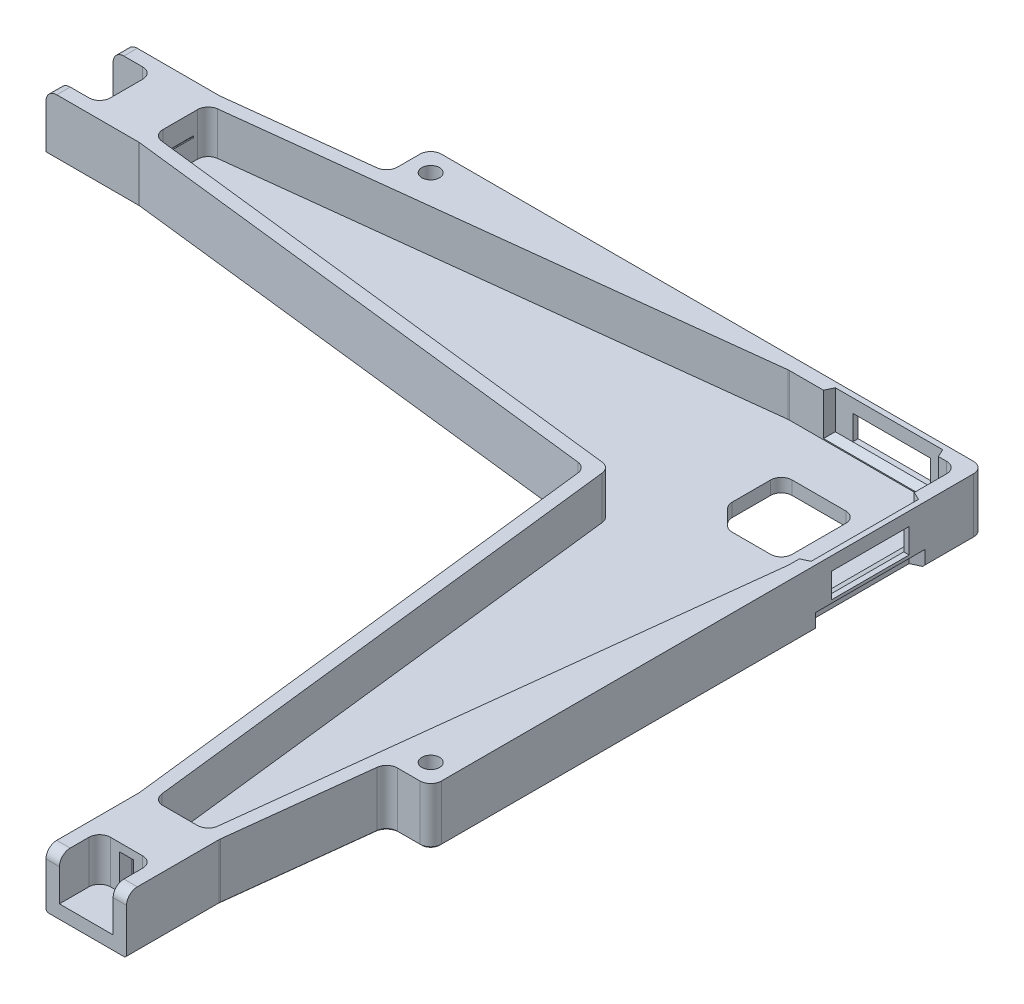
SolidWorks part; units mm, degrees
ref_plane "Front Plane" through (0, 0, 0) normal (0, 0, 1) x (1, 0, 0)
ref_plane "Top Plane" through (0, 0, 0) normal (0, 1, 0) x (1, 0, 0)
ref_plane "Right Plane" through (0, 0, 0) normal (1, 0, 0) x (0, 0, -1)
sketch "x Sensor" plane through (0, 0, 0) normal (0, 0, 1) x (1, 0, 0)
  line L0 (-13, 0) -> (0, 0) construction
  line L1 (-22.5, 1.5) -> (-13, 1.5)
  line L2 (-22.5, 1.5) -> (-22.5, -1.5)
  line L3 (-22.5, -1.5) -> (-13, -1.5)
  line L4 (-13, 1.5) -> (-13, -1.5)
  point P4 (-13, 0)
  dimension "D1" = 13
  dimension "D2" = 3
  dimension "D3" = 9.5
sketch "y Sensor" plane through (0, 0, 0) normal (1, 0, 0) x (0, 0, -1)
  line L0 (-13, 0) -> (0, 0) construction
  line L1 (-13, 1.5) -> (-22.5, 1.5)
  line L2 (-13, 1.5) -> (-13, -1.5)
  line L3 (-13, -1.5) -> (-22.5, -1.5)
  line L4 (-22.5, 1.5) -> (-22.5, -1.5)
  line L5 (0, 1.5) -> (0, -1.5) construction
  dimension "D1" = 9.5
  dimension "D2" = 13
ref_plane "y LED plane" through (-130, 0, 0) normal (1, 0, 0) x (0, 0, -1)
ref_plane "x LED plane" through (0, 0, 130) normal (0, 0, 1) x (1, 0, 0)
sketch "y LED" plane through (-130, 0, 0) normal (1, 0, 0) x (0, 0, -1)
  line L0 (-17.75, 1.5) -> (-17.75, -1.5) construction
  line L1 (-13, 1.5) -> (-22.5, 1.5) construction
  line L2 (-13, -1.5) -> (-22.5, -1.5) construction
  line L3 (-22.75, 0) -> (-12.75, 0) construction
  line L4 (-13, 0) -> (0, 0) construction
  point P10 (-17.75, 0)
  point P11 (-17.75, 0)
  dimension "D1" = 10
sketch "x LED" plane through (0, 0, 130) normal (0, 0, 1) x (1, 0, 0)
  line L0 (-17.75, 1.5) -> (-17.75, -1.5) construction
  line L1 (-22.5, 1.5) -> (-13, 1.5) construction
  line L2 (-22.5, -1.5) -> (-13, -1.5) construction
  line L3 (-22.75, 0) -> (-12.75, 0) construction
  point P9 (-17.75, 0)
  point P10 (-17.75, 0)
  dimension "D1" = 10
ref_plane "y LED cross-plane" through (0, 0, 17.75) normal (0, 0, 1) x (0, -1, 0)
ref_plane "x LED cross-plane" through (-17.75, 0, 0) normal (1, 0, 0) x (0, -1, 0)
ref_plane "Floor plane" through (0, -4, 0) normal (0, 1, 0) x (1, 0, 0)
ref_plane "Ceiling plane" through (0, 4, 0) normal (0, 1, 0) x (1, 0, 0)
sketch "Sketch10" plane through (0, -4, 0) normal (0, 1, 0) x (1, 0, 0)
  line L0 (0, 0) -> (-20, 0)
  line L1 (-20, 0) -> (-130, -12.75)
  line L2 (-130, -22.75) -> (-130, -12.75) construction
  line L3 (-130, -12.75) -> (-145, -12.75)
  line L4 (-145, -12.75) -> (-145, -22.75) construction
  line L5 (-145, -22.75) -> (-130, -22.75)
  line L6 (-130, -22.75) -> (-33.89, -33.89)
  line L7 (-20, -35.5) -> (-130, -22.75) construction
  line L8 (-33.89, -33.89) -> (-22.75, -130)
  line L9 (-22.75, -130) -> (-12.75, -130) construction
  line L10 (-22.75, -130) -> (-22.75, -145)
  line L11 (-22.75, -145) -> (-12.75, -145) construction
  line L12 (-12.75, -145) -> (-12.75, -130)
  line L13 (-12.75, -130) -> (0, -20)
  line L14 (0, -20) -> (0, 0)
  line L15 (-145, -17.75) -> (-51.5337, -17.75) construction
  line L16 (-17.75, -145) -> (-17.75, -69.9842) construction
  line L17 (-20.1444, 2.5) -> (-130.1444, -10.25)
  line L18 (-130.1444, -10.25) -> (-147.5, -10.25)
  line L19 (-147.5, -10.25) -> (-147.5, -12.75)
  line L20 (-147.5, -25.25) -> (-130.1444, -25.25)
  line L21 (-130.1444, -25.25) -> (-36.1453, -36.1453)
  line L23 (-36.1453, -36.1453) -> (-25.25, -130.1444)
  line L24 (-25.25, -130.1444) -> (-25.25, -147.5)
  line L25 (-25.25, -147.5) -> (-22.75, -147.5)
  line L26 (-10.25, -147.5) -> (-10.25, -130.1444)
  line L27 (-10.25, -130.1444) -> (2.5, -20.1444)
  line L28 (2.5, -20.1444) -> (2.5, 2.5)
  line L29 (2.5, 2.5) -> (-20.1444, 2.5)
  line L30 (-145, -12.75) -> (-147.5, -12.75)
  line L31 (-145, -22.75) -> (-147.5, -22.75)
  line L32 (-147.5, -12.75) -> (-147.5, -22.75) construction
  line L33 (-147.5, -10.25) -> (-147.5, -25.25) construction
  line L34 (-147.5, -22.75) -> (-147.5, -25.25)
  line L35 (-22.75, -145) -> (-22.75, -147.5)
  line L36 (-12.75, -145) -> (-12.75, -147.5)
  line L37 (-22.75, -147.5) -> (-12.75, -147.5) construction
  line L38 (-25.25, -147.5) -> (-10.25, -147.5) construction
  line L39 (-12.75, -147.5) -> (-10.25, -147.5)
  line L40 (-15.8451, -35.9816) -> (-33.89, -33.89) construction
  line L41 (-36.1453, -36.1453) -> (-36.1453, -36.1453) construction
  line L42 (-22.75, -130) -> (-35.5, -20) construction
  line L43 (-130.1444, -25.25) -> (-36.1453, -36.1453) construction
  line L44 (-130, -22.75) -> (-15.8451, -35.9816) construction
  dimension "D2" = 20
  dimension "D3" = 15
  dimension "D4" = 2.5
sketch "Max Shadows" plane through (0, 0, 0) normal (0, 1, 0) x (1, 0, 0)
  line L0 (-130, -17.75) -> (0, -13) construction
  line L1 (0, -13) -> (0, -22.5) construction
  line L2 (0, -22.5) -> (-130, -17.75) construction
  line L3 (0, -20) -> (0, 0) construction
  line L4 (-17.75, -130) -> (-22.5, 0) construction
  line L5 (-22.75, -130) -> (-12.75, -130) construction
  line L6 (-22.5, 0) -> (-13, 0) construction
  line L7 (0, 0) -> (-20, 0) construction
  line L8 (-17.75, -130) -> (-13, 0) construction
extrude "Boss-Extrude3" add sketch "Sketch10" along normal up to surface (8 mm away) up to plane "Ceiling plane"
sketch "Sketch12" plane through (0, -4, 0) normal (0, 1, 0) x (1, 0, 0)
  line L0 (-147.5, -12.75) -> (-147.5, -22.75) construction
  line L1 (-147.5, -10.25) -> (-147.5, -12.75) construction
  line L2 (-130.1444, -10.25) -> (-147.5, -10.25) construction
  line L3 (-20.1444, 2.5) -> (-130.1444, -10.25) construction
  line L4 (2.5, 2.5) -> (-20.1444, 2.5) construction
  line L5 (2.5, -20.1444) -> (2.5, 2.5) construction
  line L6 (-10.25, -130.1444) -> (2.5, -20.1444) construction
  line L7 (-10.25, -147.5) -> (-10.25, -130.1444) construction
  line L8 (-12.75, -147.5) -> (-10.25, -147.5) construction
  line L9 (-22.75, -147.5) -> (-12.75, -147.5) construction
  line L10 (-25.25, -147.5) -> (-22.75, -147.5) construction
  line L11 (-25.25, -130.1444) -> (-25.25, -147.5) construction
  line L12 (-36.1453, -36.1453) -> (-25.25, -130.1444) construction
  line L13 (-147.5, -22.75) -> (-147.5, -25.25) construction
  line L14 (-147.5, -25.25) -> (-130.1444, -25.25) construction
  line L15 (-130.1444, -25.25) -> (-36.1453, -36.1453) construction
  line L17 (-147.5, -12.75) -> (-147.5, -22.75)
  line L18 (-147.5, -10.25) -> (-147.5, -12.75)
  line L19 (-130.1444, -10.25) -> (-147.5, -10.25)
  line L20 (-20.1444, 2.5) -> (-130.1444, -10.25)
  line L21 (2.5, 2.5) -> (-20.1444, 2.5)
  line L22 (2.5, -20.1444) -> (2.5, 2.5)
  line L23 (-10.25, -130.1444) -> (2.5, -20.1444)
  line L24 (-10.25, -147.5) -> (-10.25, -130.1444)
  line L25 (-12.75, -147.5) -> (-10.25, -147.5)
  line L26 (-22.75, -147.5) -> (-12.75, -147.5)
  line L27 (-25.25, -147.5) -> (-22.75, -147.5)
  line L28 (-25.25, -130.1444) -> (-25.25, -147.5)
  line L29 (-36.1453, -36.1453) -> (-25.25, -130.1444)
  line L30 (-147.5, -22.75) -> (-147.5, -25.25)
  line L31 (-147.5, -25.25) -> (-130.1444, -25.25)
  line L32 (-130.1444, -25.25) -> (-36.1453, -36.1453)
extrude "Boss-Extrude4" add sketch "Sketch12" against normal blind 2.5
sketch "Sketch13" plane through (0, 0, 17.75) normal (0, 0, 1) x (0, -1, 0)
  line L0 (-4, -130) -> (-0.15, -130)
  line L1 (4, -130) -> (4, -134.05)
  line L2 (4, -147.5) -> (4, -130) construction
  line L3 (-4, -130) -> (4, -130) construction
  line L5 (0.15, -130) -> (4, -130)
  line L6 (-0.15, -130) -> (0.15, -130) construction
  line L8 (-0.15, -130) -> (-0.15, -130.2)
  line L9 (-4, -130) -> (-4, -140)
  line L10 (-4, -147.5) -> (-4, -130) construction
  line L11 (-4, -140) -> (4, -140)
  line L12 (4, -140) -> (4, -136.5)
  line L13 (4, -136.5) -> (-3, -136.5)
  line L14 (-3, -136.5) -> (-3, -133.05)
  line L15 (-0.15, -130.2) -> (-3, -133.05)
  line L16 (0, -130) -> (0, -136.5) construction
  line L17 (-2.5, -140) -> (-2.5, -136.5) construction
  line L18 (-2.5, -136.5) -> (-2.5, -135.2) construction
  line L19 (2.5, -140) -> (2.5, -136.5) construction
  line L20 (2.5, -136.5) -> (2.5, -135.2) construction
  line L21 (0.15, -130) -> (0.15, -130.2)
  line L22 (0.15, -130.2) -> (4, -134.05)
  arc A0 (-2.5, -135.2) -> (2.5, -135.2) centre (0, -135.2) cw construction
  point P13 (0, -130)
  point P26 (0, -132.7)
  dimension "D3" = 7.3
  dimension "D1" = 0.3
  dimension "D2" = 1
  dimension "D4" = 5
  dimension "D5" = 45
  dimension "D6" = 6.5
  dimension "D7" = 10
  dimension "D8" = 0.2
extrude "Boss-Extrude5" add sketch "Sketch13" along normal up to next and the other way up to next
sketch "Sketch14" plane through (-140, 0, 0) normal (-1, 0, 0) x (0, 0, 1)
  line L0 (17.75, 1.5) -> (17.75, -1.5) construction
  circle A0 centre (17.75, 0) radius 0.95
  dimension "D1" = 1.9
extrude "Cut-Extrude1" cut sketch "Sketch14" against normal up to next
sketch "Sketch38" plane through (-140, 0, 0) normal (-1, 0, 0) x (0, 0, 1)
  line L0 (17.75, 2.5) -> (17.75, -2.5) construction
  line L1 (16.45, 2.5) -> (19.05, 2.5)
  line L2 (16.45, 2.5) -> (16.45, -2.5)
  line L3 (16.45, -2.5) -> (19.05, -2.5)
  line L4 (19.05, 2.5) -> (19.05, -2.5)
  point P6 (17.75, 0)
  dimension "D1" = 5
  dimension "D2" = 2.6
extrude "Cut-Extrude20" cut sketch "Sketch38" against normal blind 2.3
sketch "Sketch15" plane through (-17.75, 0, 0) normal (1, 0, 0) x (0, -1, 0)
  line L0 (-4, -130) -> (-0.15, -130)
  line L1 (4, -130) -> (4, -134.05)
  line L5 (0.15, -130) -> (4, -130)
  line L6 (-0.15, -130) -> (0.15, -130) construction
  line L8 (-0.15, -130) -> (-0.15, -130.2)
  line L9 (-4, -130) -> (-4, -140)
  line L11 (-4, -140) -> (4, -140)
  line L12 (4, -140) -> (4, -136.5)
  line L13 (4, -136.5) -> (-3, -136.5)
  line L14 (-3, -136.5) -> (-3, -133.05)
  line L15 (-0.15, -130.2) -> (-3, -133.05)
  line L16 (0, -130) -> (0, -136.5) construction
  line L17 (-2.5, -140) -> (-2.5, -136.5) construction
  line L18 (-2.5, -136.5) -> (-2.5, -135.2) construction
  line L19 (2.5, -140) -> (2.5, -136.5) construction
  line L20 (2.5, -136.5) -> (2.5, -135.2) construction
  line L21 (0.15, -130) -> (0.15, -130.2)
  line L22 (0.15, -130.2) -> (4, -134.05)
  arc A0 (-2.5, -135.2) -> (2.5, -135.2) centre (0, -135.2) cw construction
extrude "Boss-Extrude6" add sketch "Sketch15" along normal up to next and the other way up to next
sketch "Sketch16" plane through (0, 0, 140) normal (0, 0, -1) x (-1, 0, 0)
  circle A0 centre (17.75, 0) radius 0.95
extrude "Cut-Extrude2" cut sketch "Sketch16" along normal up to next
sketch "Sketch39" plane through (0, 0, 140) normal (0, 0, 1) x (1, 0, 0)
  line L1 (-16.45, 2.5) -> (-19.05, 2.5)
  line L2 (-16.45, 2.5) -> (-16.45, -2.5)
  line L3 (-16.45, -2.5) -> (-19.05, -2.5)
  line L4 (-19.05, 2.5) -> (-19.05, -2.5)
  line L5 (-16.45, 2.5) -> (-19.05, -2.5) construction
  line L6 (-16.45, -2.5) -> (-19.05, 2.5) construction
  point P0 (-17.75, 0)
  dimension "D1" = 2.6
  dimension "D2" = 5
extrude "Cut-Extrude21" cut sketch "Sketch39" against normal blind 2.3
sketch "Sketch18" plane through (0, 0, -2.5) normal (0, 0, -1) x (-1, 0, 0)
  line L0 (-2.5, -6.5) -> (20.1444, -6.5) construction
  line L1 (-2.5, 4) -> (130.1444, 4)
  line L2 (-2.5, 4) -> (-2.5, -6.5)
  line L3 (-2.5, -6.5) -> (130.1444, -6.5)
  line L4 (130.1444, 4) -> (130.1444, -6.5)
  line L6 (130.1444, 4) -> (130.1444, -6.5) construction
extrude "Cut-Extrude4" cut sketch "Sketch18" against normal offset from surface (1.5 mm away) 1 up to face at (-10, 0, 0)
sketch "Sketch20" plane through (2.5, 0, 0) normal (1, 0, 0) x (0, 0, -1)
  line L0 (-20.1444, 4) -> (1, 4) construction
  line L1 (1, -6.5) -> (-130.1444, -6.5)
  line L2 (1, -6.5) -> (1, 4)
  line L3 (1, 4) -> (-130.1444, 4)
  line L4 (-130.1444, -6.5) -> (-130.1444, 4)
  line L5 (-130.1444, 4) -> (-130.1444, -6.5) construction
extrude "Cut-Extrude6" cut sketch "Sketch20" against normal offset from surface (1.5 mm away) 1 contours L1 L4 L3 L2 up to face at (0, 0, 10)
sketch "Sketch21" plane through (0, 0, 0) normal (0, 0, 1) x (1, 0, 0)
  line L0 (-20, -4) -> (-41.713, -4)
  line L1 (-41.713, -4) -> (-41.713, 4)
  line L2 (-41.713, 4) -> (-20, 4)
  line L3 (-33.0856, 4) -> (-130.1444, 4) construction
  line L4 (0, 4) -> (-20, 4)
  line L5 (-20, 4) -> (-20, -4)
  line L6 (-20, -4) -> (0, -4)
  line L7 (0, -4) -> (0, 4)
  line L8 (0, 4) -> (-20, 4)
  line L10 (-20, -4) -> (0, -4)
  line L11 (0, -4) -> (0, 4)
  dimension "D1" = 0
extrude "Boss-Extrude7" add sketch "Sketch21" along normal offset from surface (1.5 mm away) 2.5 up to face at (-16.0428, -1.25, -1)
sketch "Sketch22" plane through (0, 0, 0) normal (-1, 0, 0) x (0, 0, 1)
  line L0 (20, -4) -> (41.713, -4)
  line L1 (41.713, -4) -> (41.713, 4)
  line L2 (41.713, 4) -> (20, 4)
  line L4 (1.5, 4) -> (1.5, -4)
  line L5 (1.5, -4) -> (20, -4)
  line L6 (20, -4) -> (20, 4)
  line L7 (20, 4) -> (1.5, 4)
  line L8 (1.5, 4) -> (1.5, -4)
  line L9 (1.5, -4) -> (20, -4)
  line L11 (20, 4) -> (1.5, 4)
  dimension "D1" = 0
extrude "Boss-Extrude8" add sketch "Sketch22" along normal offset from surface (1.5 mm away) 2.5 up to face at (1, -1.25, 16.0428)
sketch "Sketch17" plane through (0, 0, 0) normal (0, 0, 1) x (1, 0, 0)
  line L1 (-8, -3.1) -> (-22.5, -3.1)
  line L2 (-8, -3.1) -> (-8, 1.5)
  line L3 (-8, 1.5) -> (-22.5, 1.5)
  line L4 (-22.5, -3.1) -> (-22.5, 1.5)
  dimension "D1" = 14.5
  dimension "D2" = 4.6
extrude "Cut-Extrude3" cut sketch "Sketch17" against normal through all and the other way up to next
sketch "Sketch19" plane through (0, 0, 0) normal (1, 0, 0) x (0, 0, -1)
  line L1 (-13, -3.1) -> (-27.5, -3.1)
  line L2 (-13, -3.1) -> (-13, 1.5)
  line L3 (-13, 1.5) -> (-27.5, 1.5)
  line L4 (-27.5, -3.1) -> (-27.5, 1.5)
  dimension "D1" = 14.5
  dimension "D2" = 4.6
extrude "Cut-Extrude5" cut sketch "Sketch19" along normal through all and the other way up to next
sketch "Sketch23" plane through (-1.5, 0, 0) normal (-1, 0, 0) x (0, 0, 1)
  line L0 (27.5, -3.1) -> (13, -3.1) construction
  line L1 (10.25, 1.5) -> (30.25, 1.5)
  line L2 (10.25, 1.5) -> (10.25, -3.1)
  line L3 (10.25, -3.1) -> (30.25, -3.1)
  line L4 (30.25, 1.5) -> (30.25, -3.1)
  point P4 (20.25, -3.1)
  point P7 (20.25, -3.1)
  dimension "D1" = 20
extrude "Cut-Extrude7" cut sketch "Sketch23" against normal up to surface (1.5 mm away) up to plane "Right Plane"
sketch "Sketch25" plane through (-36, 0, 1.5) normal (0, 0, 1) x (1, 0, 0)
  line L1 (10.25, 1.5) -> (30.25, 1.5)
  line L2 (10.25, 1.5) -> (10.25, -3.1)
  line L3 (10.25, -3.1) -> (30.25, -3.1)
  line L4 (30.25, 1.5) -> (30.25, -3.1)
extrude "Cut-Extrude9" cut sketch "Sketch25" against normal up to surface (1.5 mm away) up to plane "Front Plane"
chamfer "Chamfer2" distance 1.5 angle 25 6 edges at (-1.5, -3.1, 20.25) (-1.5, -0.8, 30.25) (-1.5, -0.8, 10.25) (-5.75, -0.8, 1.5) (-25.75, -0.8, 1.5) (-15.75, -3.1, 1.5) first distance on face at (-0.125, -3.1, 20.25) first distance on face at (-0.75, -0.8, 30.25) first distance on face at (-0.75, -0.8, 10.25) first distance on face at (-5.75, -0.8, 0.75) first distance on face at (-25.75, -0.8, 0.75) first distance on face at (-15.5, -3.1, 0.125)
sketch "Sketch28" plane through (0, 0, -1) normal (0, 0, -1) x (-1, 0, 0)
  line L0 (-1, -6.5) -> (33.0856, -6.5) construction
  line L1 (24.5, -4.6) -> (6, -4.6)
  line L2 (24.5, -4.6) -> (24.5, -6.5)
  line L3 (24.5, -6.5) -> (6, -6.5)
  line L4 (6, -4.6) -> (6, -6.5)
  line L7 (22.5, -3.1) -> (8, -3.1) construction
  line L8 (8, -3.1) -> (8, 1.5) construction
  line L10 (22.5, 1.5) -> (22.5, -3.1) construction
  dimension "D1" = 1.5
  dimension "D2" = 2
  dimension "D3" = 2
extrude "Cut-Extrude10" cut sketch "Sketch28" against normal blind 2
sketch "Sketch29" plane through (1, 0, 5) normal (-1, 0, 0) x (0, 0, 1)
  line L0 (22.5, -3.1) -> (8, -3.1) construction
  line L1 (24.5, -4.6) -> (6, -4.6)
  line L2 (24.5, -4.6) -> (24.5, -6.5)
  line L3 (24.5, -6.5) -> (6, -6.5)
  line L4 (6, -4.6) -> (6, -6.5)
  line L5 (22.5, 1.5) -> (22.5, -3.1) construction
  line L6 (8, -3.1) -> (8, 1.5) construction
  line L7 (28.0856, -6.5) -> (-6, -6.5) construction
  dimension "D1" = 1.5
  dimension "D2" = 2
  dimension "D3" = 2
extrude "Cut-Extrude11" cut sketch "Sketch29" along normal blind 2
chamfer "Chamfer3" distance 2 angle 25 6 edges at (-24.5, -5.55, -1) (-15.25, -4.6, -1) (-6, -5.55, -1) (1, -5.55, 11) (1, -5.55, 29.5) (1, -4.6, 20.25) first distance on face at (-24.5, -5.55, 0) first distance on face at (-15.25, -4.6, 0) first distance on face at (-6, -5.55, 0) first distance on face at (0, -5.55, 11) first distance on face at (0, -5.55, 29.5) first distance on face at (0, -4.6, 20.25)
sketch "Sketch30" plane through (0, -4, 0) normal (0, 1, 0) x (1, 0, 0)
  line L0 (-13.493, -13.493) -> (-21.7069, -21.7069) construction
  line L1 (-13.8037, -21.9956) -> (-21.9956, -13.8037) construction
  line L2 (-130, -17.75) -> (0, -13) construction
  line L3 (-17.75, -130) -> (-22.5, 0) construction
  line L4 (0, -22.5) -> (-130, -17.75) construction
  line L5 (-17.75, -130) -> (-13, 0) construction
  line L7 (-10.8997, -10.8997) -> (-24.8997, -10.8997)
  line L8 (-10.8997, -10.8997) -> (-10.8997, -24.8997)
  line L9 (-10.8997, -24.8997) -> (-24.8997, -24.8997)
  line L10 (-24.8997, -10.8997) -> (-24.8997, -24.8997)
  line L11 (-10.8997, -10.8997) -> (-24.8997, -24.8997) construction
  line L12 (-10.8997, -24.8997) -> (-24.8997, -10.8997) construction
  point P12 (-17.8997, -17.8997)
  point P13 (-17.8997, -17.8997)
  dimension "D1" = 14
extrude "Cut-Extrude12" cut sketch "Sketch30" against normal through all
fillet "Fillet1" radius 2 3 edges at (-10.8997, -5.25, 10.8997) (-10.8997, -5.25, 24.8997) (-24.8997, -5.25, 10.8997)
sketch "Sketch31" plane through (0, -0.15, 0) normal (0, 1, 0) x (1, 0, 0)
  line L0 (-130.2, -12.75) -> (-130.2, -22.75) construction
  line L1 (-130, -12.75) -> (-130.2, -12.75)
  line L2 (-130, -12.75) -> (-130, -15.25)
  line L3 (-130, -15.25) -> (-130.2, -15.25)
  line L4 (-130.2, -12.75) -> (-130.2, -15.25)
  line L6 (-130, -22.75) -> (-130.2, -22.75)
  line L7 (-130, -22.75) -> (-130, -20.25)
  line L8 (-130, -20.25) -> (-130.2, -20.25)
  line L9 (-130.2, -22.75) -> (-130.2, -20.25)
  dimension "D1" = 5
extrude "Boss-Extrude9" add sketch "Sketch31" along normal up to next
sketch "Sketch32" plane through (0, -0.15, 0) normal (0, 1, 0) x (1, 0, 0)
  line L0 (-22.75, -130.2) -> (-12.75, -130.2) construction
  line L1 (-22.75, -130) -> (-20.25, -130)
  line L2 (-22.75, -130) -> (-22.75, -130.2)
  line L3 (-22.75, -130.2) -> (-20.25, -130.2)
  line L4 (-20.25, -130) -> (-20.25, -130.2)
  line L6 (-12.75, -130) -> (-15.25, -130)
  line L7 (-12.75, -130) -> (-12.75, -130.2)
  line L8 (-12.75, -130.2) -> (-15.25, -130.2)
  line L9 (-15.25, -130) -> (-15.25, -130.2)
  dimension "D1" = 5
extrude "Boss-Extrude10" add sketch "Sketch32" along normal up to next
sketch "Sketch33" plane through (0, -6.5, 0) normal (0, -1, 0) x (1, 0, 0)
  line L0 (1, -1) -> (-36.1453, 36.1453) construction
  line L2 (-33.0856, -1) -> (-130.1444, 10.25) construction
  line L3 (-33.0856, -1) -> (-102.1052, -1)
  line L4 (-33.0856, -1) -> (-102.1052, 7)
  line L5 (1, 102.1052) -> (-7, 102.1052)
  line L6 (-102.1052, -1) -> (-102.1052, 7)
  line L7 (1, 33.0856) -> (-7, 102.1052)
  line L8 (1, 33.0856) -> (1, 102.1052)
  dimension "D1" = 8
extrude "Boss-Extrude11" add sketch "Sketch33" against normal up to surface (10.5 mm away) up to face at (-66.976, 4, 66.976)
sketch "Sketch35" plane through (0, 4, 0) normal (0, 1, 0) x (1, 0, 0)
  line L0 (1, 1) -> (-36.1453, -36.1453) construction
  line L2 (-102.1052, -7) -> (-102.1052, 1) construction
  line L3 (1, 1) -> (-102.1052, 1) construction
  circle A0 centre (-98.1052, -3) radius 1.65
  circle A1 centre (-3, -98.1052) radius 1.65
  dimension "D1" = 4
  dimension "D3" = 3.3
  dimension "D2" = 4
extrude "Cut-Extrude13" cut sketch "Sketch35" against normal through all
fillet "Fillet2" radius 2 26 edges at (-140, 0, 12.75) (-140, 0, 22.75) (-22.75, 0, 140) (-12.75, 0, 140) (-147.5, 4, 11.5) (-147.5, 4, 24) (-130.1444, -1.25, 10.25) (1, -1.25, -1) (-10.25, -1.25, 130.1444) (-25.25, -1.25, 130.1444) (-130.1444, -1.25, 25.25) (-1.5, 0, 32.9412) (-1.5, 0, 1.5) (-32.9412, 0, 1.5) (-130, 0, 12.75) (-130, 0, 22.75) (-12.75, 0, 130) (-22.75, 0, 130) (-102.1052, -1.25, -1) (-102.1052, -1.25, 7) (1, -1.25, 102.1052) (-7, -1.25, 102.1052) (-11.5, 4, 147.5) (-24, 4, 147.5) (-33.89, 0, 33.89) (-36.1453, -1.25, 36.1453)
chamfer "Chamfer4" distance 0.3 angle 45 24 edges at (-62.7689, -6.5, -1) (-101.5194, -6.5, -0.4142) (-102.1052, -6.5, 3.1092) (-102.6118, -6.5, 6.5487) (-116.9523, -6.5, 8.7209) (-130.1446, -6.5, 10.2467) (-138.88, -6.5, 10.25) (-3.0337, -6.5, -1) (0.4142, -6.5, -0.4142) (1, -6.5, 5.5337) (1, -6.5, 65.2689) (0.4142, -6.5, 101.5194) (-3.1092, -6.5, 102.1052) (-6.5487, -6.5, 102.6118) (-8.7209, -6.5, 116.9523) (-10.2467, -6.5, 130.1446) (-10.25, -6.5, 138.88) (-25.25, -6.5, 138.88) (-25.2533, -6.5, 130.1446) (-30.6131, -6.5, 83.8745) (-83.8745, -6.5, 30.6131) (-130.1446, -6.5, 25.2533) (-138.88, -6.5, 25.25) (-36.5354, -6.5, 36.5354)
chamfer "Chamfer5" distance 4 angle 45 1 edges at (-24.8997, -5.25, 24.8997)
fillet "Fillet3" radius 2 2 edges at (-20.8997, -5.25, 24.8997) (-24.8997, -5.25, 20.8997)
sketch "Sketch37" plane through (0, 1.5, 0) normal (0, -1, 0) x (1, 0, 0)
  line L0 (1, 27.5) -> (0, 27.5) construction
  line L1 (0, 27.5) -> (0, 30.25) construction
  line L2 (0, 30.25) -> (-1.5, 30.9495) construction
  line L3 (-1.5, 30.9495) -> (-1.5, 9.5505) construction
  line L4 (-1.5, 9.5505) -> (0, 10.25) construction
  line L5 (0, 10.25) -> (0, 13) construction
  line L6 (0, 13) -> (1, 13) construction
  line L7 (1, 13) -> (1, 27.5) construction
  line L8 (-25.75, 0) -> (-22.5, 0) construction
  line L9 (-22.5, 0) -> (-22.5, -1) construction
  line L10 (-22.5, -1) -> (-8, -1) construction
  line L11 (-8, -1) -> (-8, 0) construction
  line L12 (-8, 0) -> (-5.75, 0) construction
  line L13 (-5.75, 0) -> (-5.0505, 1.5) construction
  line L14 (-5.0505, 1.5) -> (-26.4495, 1.5) construction
  line L15 (-26.4495, 1.5) -> (-25.75, 0) construction
  line L16 (1, 27.5) -> (0, 27.5) construction
  line L17 (0, 27.5) -> (0, 30.25)
  line L18 (0, 30.25) -> (-1.5, 30.9495)
  line L19 (-1.5, 30.9495) -> (-1.5, 9.5505)
  line L20 (-1.5, 9.5505) -> (0, 10.25)
  line L21 (0, 10.25) -> (0, 13)
  line L22 (0, 13) -> (1, 13) construction
  line L23 (1, 13) -> (1, 27.5) construction
  line L24 (-25.75, 0) -> (-22.5, 0)
  line L25 (-22.5, 0) -> (-22.5, -1) construction
  line L26 (-22.5, -1) -> (-8, -1) construction
  line L27 (-8, -1) -> (-8, 0) construction
  line L28 (-8, 0) -> (-5.75, 0)
  line L29 (-5.75, 0) -> (-5.0505, 1.5)
  line L30 (-5.0505, 1.5) -> (-26.4495, 1.5)
  line L31 (-26.4495, 1.5) -> (-25.75, 0)
  line L32 (-22.5, 0) -> (-8, 0)
  line L33 (0, 13) -> (0, 27.5)
extrude "Cut-Extrude14" cut sketch "Sketch37" against normal through all
equation "\"D1@Sketch39\"=\"D2@Sketch38\""
equation "\"D2@Sketch39\"=\"D1@Sketch38\""
equation "\"D1@Cut-Extrude21\"=\"D1@Cut-Extrude20\""
